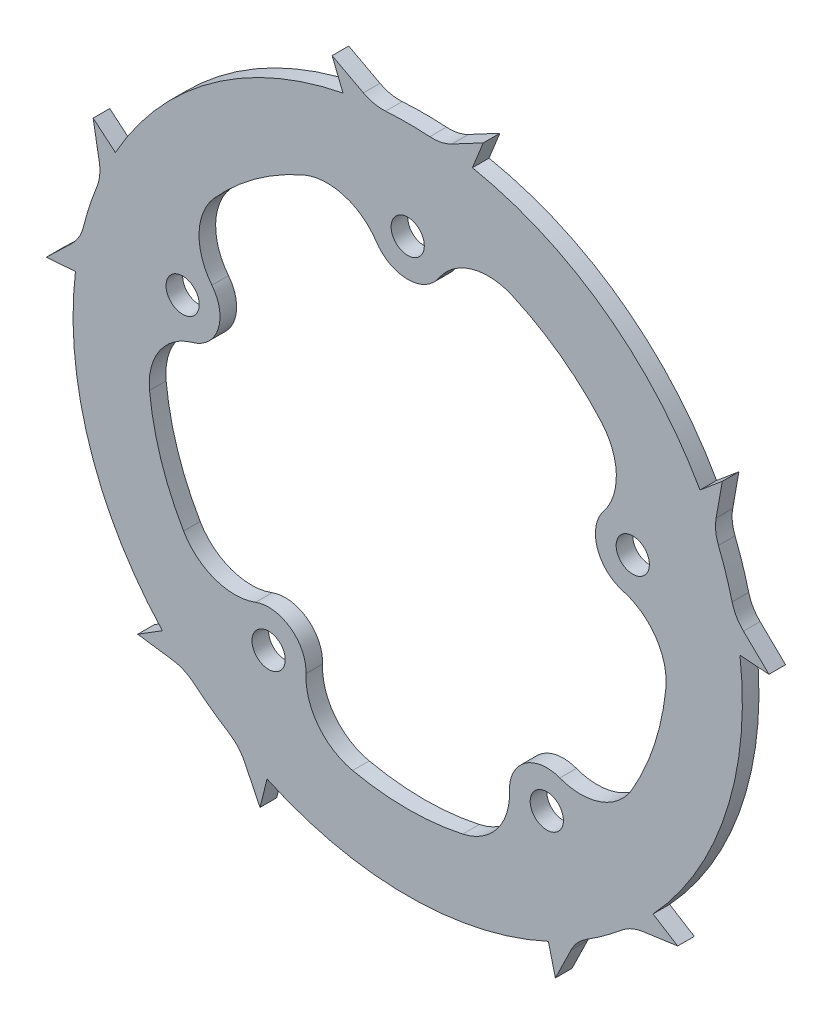
SolidWorks part; units mm, degrees
material "Alloy Steel (SS)"
ref_plane "Front Plane" through (0, 0, 0) normal (0, 0, 1) x (1, 0, 0)
ref_plane "Top Plane" through (0, 0, 0) normal (0, 1, 0) x (1, 0, 0)
ref_plane "Right Plane" through (0, 0, 0) normal (1, 0, 0) x (0, 0, -1)
sketch "Sketch1" plane through (0, 0, 0) normal (0, 0, 1) x (1, 0, 0)
  line L0 (0, 0) -> (0, 28.956) construction
  line L1 (0, 0) -> (27.5388, 8.9479) construction
  line L2 (0, 0) -> (17.0199, -23.4259) construction
  line L3 (0, 0) -> (-17.0199, -23.4259) construction
  line L4 (0, 0) -> (-27.5388, 8.9479) construction
  line L5 (-7.9162, 40.1776) -> (-9.25, 43.4769)
  line L6 (-9.25, 43.4769) -> (0, 0) construction
  line L7 (-9.25, 43.4769) -> (-5.4243, 41.4437)
  line L8 (0, 0) -> (0, 44.45) construction
  line L9 (7.9162, 40.1776) -> (9.25, 43.4769)
  line L10 (9.25, 43.4769) -> (5.4243, 41.4437)
  line L11 (-8.5217, 40.0535) -> (15.957, 45.2615) construction
  line L12 (-9.25, 43.4769) -> (-2.443, 44.9251) construction
  circle A0 centre (0, 0) radius 44.45 construction
  circle A1 centre (0, 0) radius 31.75
  circle A2 centre (0, 28.956) radius 2.032
  arc A3 (3.81, 26.4287) -> (-3.81, 26.4287) centre (0, 28.956) cw
  arc A4 (3.81, 26.4287) -> (12.7862, 29.0616) centre (9.8617, 22.4145) cw
  arc A5 (-3.81, 26.4287) -> (-12.7862, 29.0616) centre (-9.8617, 22.4145) ccw
  arc A6 (23.9579, 11.7905) -> (23.6881, 21.1409) centre (18.2701, 16.3055) ccw
  arc A7 (26.3126, 4.5434) -> (23.9579, 11.7905) centre (27.5388, 8.9479) cw
  circle A8 centre (27.5388, 8.9479) radius 2.032
  arc A9 (26.3126, 4.5434) -> (31.5904, -3.1798) centre (24.3649, -2.4525) cw
  arc A10 (18.6168, -19.1418) -> (27.4262, -15.9958) centre (21.1532, -12.3372) ccw
  arc A11 (12.4521, -23.6208) -> (18.6168, -19.1418) centre (17.0199, -23.4259) cw
  circle A12 centre (17.0199, -23.4259) radius 2.032
  arc A13 (12.4521, -23.6208) -> (6.7378, -31.0268) centre (5.1967, -23.9303) cw
  arc A14 (-12.4521, -23.6208) -> (-6.7378, -31.0268) centre (-5.1967, -23.9303) ccw
  arc A15 (-18.6168, -19.1418) -> (-12.4521, -23.6208) centre (-17.0199, -23.4259) cw
  circle A16 centre (-17.0199, -23.4259) radius 2.032
  arc A17 (-18.6168, -19.1418) -> (-27.4262, -15.9958) centre (-21.1532, -12.3372) cw
  arc A18 (-26.3126, 4.5434) -> (-31.5904, -3.1798) centre (-24.3649, -2.4525) ccw
  arc A19 (-23.9579, 11.7905) -> (-26.3126, 4.5434) centre (-27.5388, 8.9479) cw
  circle A20 centre (-27.5388, 8.9479) radius 2.032
  arc A21 (-23.9579, 11.7905) -> (-23.6881, 21.1409) centre (-18.2701, 16.3055) cw
  circle A22 centre (0, 0) radius 40.95
  arc A23 (-5.4243, 41.4437) -> (-2.7047, 40.8606) centre (-3.0402, 45.9295) ccw
  arc A24 (5.4243, 41.4437) -> (2.7047, 40.8606) centre (3.0402, 45.9295) cw
  point P47 (0, 0)
  point P57 (-6.9906, 42.4092)
  point P58 (-6.5198, 42.0959)
  point P59 (-3.5246, 40.798)
  dimension "D1" = 88.9
  dimension "D2" = 63.5
  dimension "D3" = 4.064
  dimension "D4" = 28.956
  dimension "D6" = 2.54
  dimension "D8" = 3.5
  dimension "D12" = 5.08
  dimension "D10" = 40
  dimension "D7" = 7.62
  dimension "D9" = 10
  dimension "D11" = 18.5
  dimension "D5" = 5
extrude "Boss-Extrude1" add sketch "Sketch1" along normal blind 2.032 contours A0 A1 | A19 A21 A1 A18 A20 | A5 A3 A4 A1 A2 | A7 A9 A1 A6 A8 | A11 A13 A1 A10 A12 | A15 A17 A1 A14 A16 region at (-5.1709, 39.4543, 0) region at (31.6842, -1.5906, 0) region at (7.7428, 29.6383, 0) region at (18.5119, -25.4794, 0) region at (-25.7875, 16.5223, 0) region at (-18.5119, -25.4794, 0)
extrude "Boss-Extrude5" add sketch "Sketch1<5>" along normal up to surface (2.032 mm away) up to face at (0, 0, 2.032)
sketch "Sketch1<5>" plane through (0, 0, 0) normal (0, 0, 1) x (1, 0, 0) same geometry as "Sketch1"
pattern_circular "CirPattern2" count 5 over 360 about axis through (0, 0, 2.032) along (0, 0, 1) of "Boss-Extrude5"
